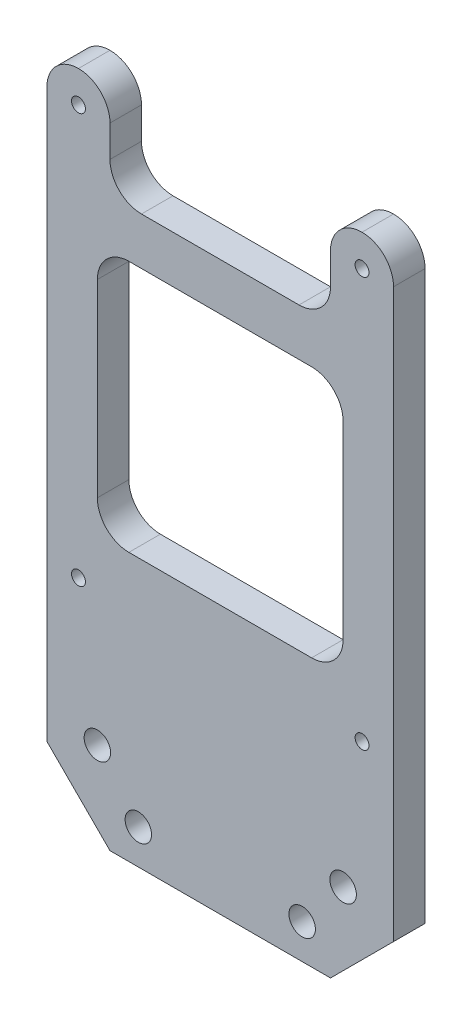
SolidWorks part; units mm, degrees
ref_plane "前视基准面" through (0, 0, 0) normal (0, 0, 1) x (1, 0, 0)
ref_plane "上视基准面" through (0, 0, 0) normal (0, 1, 0) x (1, 0, 0)
ref_plane "右视基准面" through (0, 0, 0) normal (1, 0, 0) x (0, 0, -1)
sketch "草图1" plane through (0, 0, 0) normal (0, 0, 1) x (1, 0, 0)
  line L0 (-27.5, 52.5) -> (-27.5, 47.5) construction
  line L1 (-27.5, 52.5) -> (27.5, 52.5)
  line L2 (-27.5, 52.5) -> (-27.5, -52.5)
  line L3 (-27.5, -52.5) -> (27.5, -52.5)
  line L4 (27.5, 52.5) -> (27.5, -52.5)
  line L5 (-27.5, 52.5) -> (27.5, -52.5) construction
  line L6 (-27.5, -52.5) -> (27.5, 52.5) construction
  line L7 (-27.5, 47.5) -> (-22.5, 47.5) construction
  line L8 (0, 0) -> (0, 8.75) construction
  line L9 (0, 0) -> (10, 0) construction
  line L10 (-22.5, 47.5) -> (-22.5, -17.5) construction
  circle A0 centre (-22.5, 47.5) radius 1.1
  circle A1 centre (22.5, 47.5) radius 1.1
  circle A2 centre (-22.5, -17.5) radius 1.1
  circle A3 centre (22.5, -17.5) radius 1.1
  point P0 (0, 0)
  dimension "D3" = 35
  dimension "D5" = 45
  dimension "D1" = 55
  dimension "D2" = 65
  dimension "D4" = 5
extrude "凸台-拉伸1" add sketch "草图1" along normal blind 5
chamfer "倒角1" distance 10 angle 45 2 edges at (-27.5, -52.5, 2.5) (27.5, -52.5, 2.5)
sketch "草图4" plane through (0, 0, 0) normal (0, 0, -1) x (-1, 0, 0)
  line L0 (0, -52.5) -> (-13, -52.5) construction
  line L1 (17.5, -52.5) -> (-17.5, -52.5) construction
  line L2 (-13, -52.5) -> (-13, -47) construction
  line L3 (-13, -47) -> (-13, -39) construction
  line L4 (-13, -39) -> (-19.5, -39) construction
  line L5 (0, -52.5) -> (0, -43) construction
  circle A0 centre (-13, -47) radius 2.1
  circle A1 centre (-19.5, -39) radius 2.1
  circle A2 centre (19.5, -39) radius 2.1
  circle A3 centre (13, -47) radius 2.1
extrude "切除-拉伸1" cut sketch "草图4" against normal blind 10
sketch "草图5" plane through (0, 0, 5) normal (0, 0, 1) x (1, 0, 0)
  line L0 (0, 0) -> (0, 52.5) construction
  line L1 (27.5, 52.5) -> (-27.5, 52.5) construction
  line L6 (-22.5, 47.5) -> (-22.5, 52.5) construction
  line L7 (27.5, 52.5) -> (-27.5, 52.5) construction
  line L8 (-22.5, 52.5) -> (-17.5, 52.5) construction
  line L9 (-17.5, 52.5) -> (-17.5, 37.5)
  line L10 (17.5, 52.5) -> (17.5, 37.5)
  line L11 (-17.5, 37.5) -> (17.5, 37.5)
  line L13 (-17.5, 52.5) -> (17.5, 52.5)
  point P13 (0, 37)
extrude "切除-拉伸2" cut sketch "草图5" against normal blind 10
sketch "草图6" plane through (0, 0, 5) normal (0, 0, 1) x (1, 0, 0)
  line L0 (-22.5, -17.5) -> (-22.5, 16) construction
  line L1 (-22.5, 16) -> (0, 16) construction
  line L2 (0, 0) -> (0, 10) construction
  line L4 (-19.5, 30) -> (19.5, 30)
  line L5 (-19.5, 30) -> (-19.5, -10)
  line L6 (-19.5, -10) -> (19.5, -10)
  line L7 (19.5, 30) -> (19.5, -10)
  line L8 (-19.5, 30) -> (19.5, -10) construction
  line L9 (-19.5, -10) -> (19.5, 30) construction
extrude "切除-拉伸3" cut sketch "草图6" against normal blind 10
fillet "圆角3" radius 5 4 edges at (-19.5, -10, 2.5) (19.5, -10, 2.5) (19.5, 30, 2.5) (-19.5, 30, 2.5)
fillet "圆角4" radius 5 6 edges at (17.5, 52.5, 2.5) (27.5, 52.5, 2.5) (-27.5, 52.5, 2.5) (-17.5, 52.5, 2.5) (17.5, 37.5, 2.5) (-17.5, 37.5, 2.5)
